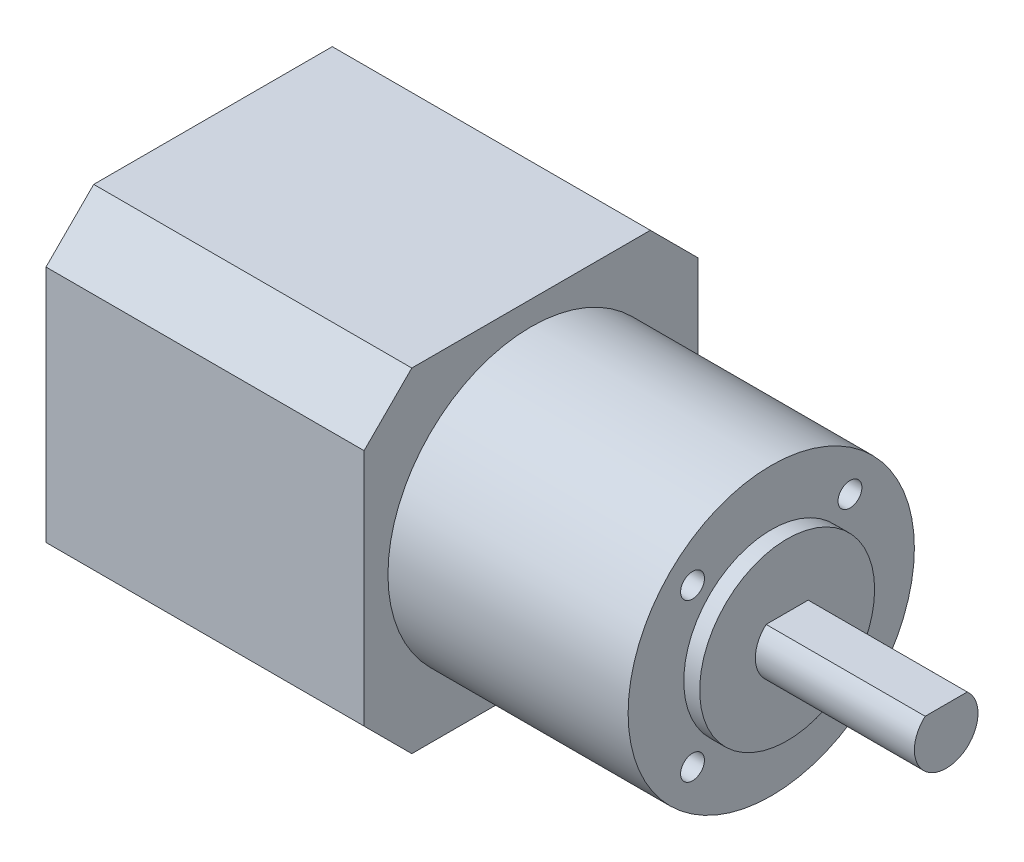
SolidWorks part; units mm, degrees
ref_plane "Front Plane" through (0, 0, 0) normal (0, 0, 1) x (1, 0, 0)
ref_plane "Top Plane" through (0, 0, 0) normal (0, 1, 0) x (1, 0, 0)
ref_plane "Right Plane" through (0, 0, 0) normal (1, 0, 0) x (0, 0, -1)
sketch "Sketch1" plane through (0, 0, 0) normal (1, 0, 0) x (0, 0, -1)
  line L0 (-21, 15) -> (-15, 21)
  line L1 (-15, -21) -> (15, -21)
  line L2 (-21, -15) -> (-21, 15)
  line L3 (-15, 21) -> (15, 21)
  line L4 (21, -15) -> (21, 15)
  line L5 (-21, -21) -> (21, 21) construction
  line L6 (-21, 21) -> (21, -21) construction
  line L7 (15, 21) -> (21, 15)
  line L8 (15, -21) -> (21, -15)
  line L9 (-21, -15) -> (-15, -21)
  point P0 (0, 0)
  dimension "D1" = 42
  dimension "D12" = 6
  dimension "D13" = 6
  dimension "D14" = 6
  dimension "D15" = 6
  dimension "D2" = 42
extrude "Boss-Extrude1" add sketch "Sketch1" along normal blind 40
sketch "Sketch2" plane through (40, 0, 0) normal (1, 0, 0) x (0, 0, -1)
  line L0 (0, 0) -> (24.4009, -24.4009) construction
  line L3 (-15, 21) -> (-21, 15) construction
  circle A0 centre (0, 0) radius 18
  circle A1 centre (0, 0) radius 14 construction
  circle A2 centre (-9.8995, 9.8995) radius 1.5
  circle A3 centre (9.8995, 9.8995) radius 1.5
  circle A4 centre (9.8995, -9.8995) radius 1.5
  circle A5 centre (-9.8995, -9.8995) radius 1.5
  point P13 (-18, 18)
  dimension "D1" = 36
  dimension "D2" = 28
  dimension "D3" = 3
  dimension "D4" = 4
extrude "Boss-Extrude2" add sketch "Sketch2" along normal blind 30.2
sketch "Sketch3" plane through (70.2, 0, 0) normal (1, 0, 0) x (0, 0, -1)
  circle A0 centre (0, 0) radius 11
  dimension "D1" = 22
extrude "Boss-Extrude3" add sketch "Sketch3" along normal blind 2
sketch "Sketch4" plane through (72.2, 0, 0) normal (1, 0, 0) x (0, 0, -1)
  line L0 (2.6458, 3) -> (-2.6458, 3)
  arc A0 (-2.6458, 3) -> (2.6458, 3) centre (0, 0) ccw
  dimension "D1" = 8
  dimension "D2" = 3
extrude "Boss-Extrude4" add sketch "Sketch4" along normal blind 20
